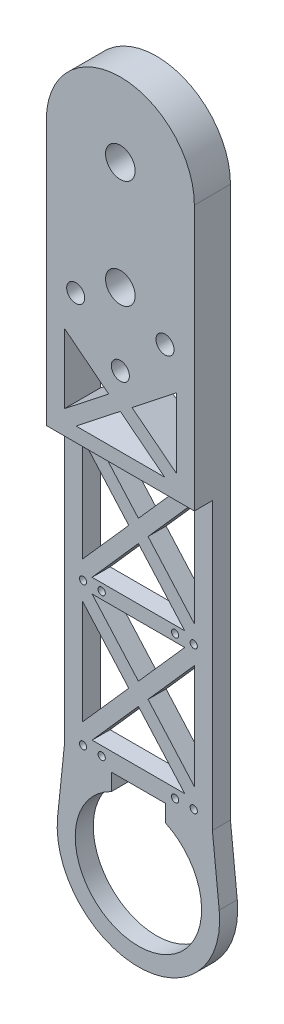
SolidWorks part; units mm, degrees
ref_plane "정면" through (0, 0, 0) normal (0, 0, 1) x (1, 0, 0)
ref_plane "윗면" through (0, 0, 0) normal (0, 1, 0) x (1, 0, 0)
ref_plane "우측면" through (0, 0, 0) normal (1, 0, 0) x (0, 0, -1)
sketch "스케치1" plane through (0, 0, 0) normal (0, 0, 1) x (1, 0, 0)
  line L0 (-20.5, 0) -> (-20.5, 173)
  line L1 (20.5, 0) -> (20.5, 173)
  line L2 (20.5, 173) -> (-20.5, 173) construction
  line L3 (-20.5, 143) -> (20.5, 143) construction
  circle A0 centre (0, 0) radius 20.5
  circle A1 centre (0, 0) radius 15.5 construction
  circle A2 centre (-15.5, 0) radius 1.5
  circle A3 centre (-7.75, 13.4234) radius 1.5
  circle A4 centre (7.75, 13.4234) radius 1.5
  circle A5 centre (15.5, 0) radius 1.5
  circle A6 centre (7.75, -13.4234) radius 1.5
  circle A7 centre (-7.75, -13.4234) radius 1.5
  circle A8 centre (0, -7) radius 6.5
  circle A9 centre (0, 173) radius 20.5
  point P19 (0, 0)
  dimension "D1" = 31
  dimension "D2" = 3
  dimension "D4" = 13
  dimension "D6" = 5
  dimension "D5" = 7
  dimension "D7" = 180
  dimension "D8" = 30
  dimension "D3" = 6
extrude "보스-돌출1" add sketch "스케치1" against normal blind 10 contours A9 L0 A0 L1 | A9 | A0 A8 A7 A6 A5 A4 A3 A2 region at (0, 86.5, 0) region at (0, 0.8114, 0) region at (0, 173, 0)
sketch "스케치2" plane through (0, 0, 0) normal (0, 0, 1) x (1, 0, 0)
  line L0 (-20.5, 143) -> (20.5, 143) construction
  circle A0 centre (0, 173) radius 4.1
  circle A1 centre (0, 143) radius 4.1
  dimension "D1" = 8.2
  dimension "D2" = 8.2
extrude "컷-돌출1" cut sketch "스케치2" against normal blind 10
sketch "스케치3" plane through (0, 0, 0) normal (0, 0, 1) x (1, 0, 0)
  line L0 (-20.5, 133) -> (20.5, 133) construction
  line L1 (-20.5, 0) -> (-20.5, 173) construction
  line L2 (20.5, 0) -> (20.5, 173) construction
  line L3 (-15.5, 128) -> (15.5, 103.625) construction
  line L4 (-20.5, 143) -> (20.5, 143) construction
  line L5 (-20.5, 20.5) -> (20.5, 20.5) construction
  line L6 (-15.5, 128) -> (15.5, 128)
  line L7 (-15.5, 128) -> (-15.5, 25.5)
  line L8 (-15.5, 25.5) -> (15.5, 25.5)
  line L9 (15.5, 128) -> (15.5, 25.5)
  line L10 (-15.5, 125.4558) -> (12.2643, 103.625)
  line L11 (-12.2643, 128) -> (15.5, 106.1692)
  line L12 (15.5, 128) -> (-15.5, 103.625) construction
  line L13 (12.2643, 128) -> (-15.5, 106.1692)
  line L14 (15.5, 125.4558) -> (-12.2643, 103.625)
  line L15 (-15.5, 99.625) -> (15.5, 99.625)
  line L16 (-15.5, 62.56) -> (15.5, 62.56) construction
  line L17 (-15.5, 64.56) -> (15.5, 64.56)
  line L18 (-15.5, 60.56) -> (15.5, 60.56)
  line L19 (-15.5, 99.625) -> (15.5, 64.56) construction
  line L20 (-15.5, 64.56) -> (15.5, 99.625) construction
  line L21 (15.5, 60.56) -> (-15.5, 25.5) construction
  line L22 (-15.5, 60.56) -> (15.5, 25.5) construction
  line L23 (-12.8305, 99.625) -> (15.5, 67.5796)
  line L24 (15.5, 103.625) -> (-15.5, 103.625)
  line L25 (-15.5, 96.6054) -> (12.8305, 64.56)
  line L26 (12.8305, 99.625) -> (-15.5, 67.5796)
  line L27 (15.5, 96.6054) -> (-12.8305, 64.56)
  line L28 (-12.8303, 60.56) -> (15.5, 28.5193)
  line L29 (-15.5, 57.5407) -> (12.8303, 25.5)
  line L30 (12.8303, 60.56) -> (-15.5, 28.5193)
  line L31 (15.5, 57.5407) -> (-12.8303, 25.5)
  circle A0 centre (0, 0) radius 20.5 construction
  point P6 (0, 71.75)
  dimension "D1" = 10
  dimension "D2" = 5
  dimension "D3" = 5
  dimension "D4" = 5
  dimension "D5" = 5
  dimension "D6" = 20.5
  dimension "D7" = 24.375
  dimension "D8" = 2
  dimension "D9" = 2
  dimension "D10" = 2
  dimension "D11" = 2
  dimension "D12" = 4
  dimension "D13" = 37.065
  dimension "D14" = 2
  dimension "D15" = 2
  dimension "D16" = 2
  dimension "D17" = 2
  dimension "D18" = 2
  dimension "D19" = 2
  dimension "D20" = 2
  dimension "D21" = 2
  dimension "D22" = 2
  dimension "D23" = 2
sketch "스케치4" plane through (0, 0, 0) normal (0, 0, 1) x (1, 0, 0)
  line L7 (-20.5, 0) -> (-20.5, 173) construction
  line L8 (20.5, -20.5) -> (-20.5, -20.5)
  line L9 (20.5, -20.5) -> (20.5, 99.625)
  line L10 (20.5, 99.625) -> (-20.5, 99.625)
  line L11 (-20.5, -20.5) -> (-20.5, 99.625)
  line L12 (-15.5, 99.625) -> (15.5, 99.625) construction
  dimension "D1" = 0
extrude "컷-돌출3" cut sketch "스케치4" against normal blind 5
extrude "컷-돌출4" cut sketch "스케치3" against normal blind 10 and the other way through all contours L9 L14 L11 | L24 L10 L14 | L13 L10 L7 region at (-11.4119, 115.8125, 0) region at (11.4119, 115.8125, 0) region at (0, 106.8394, 0)
extrude "컷-돌출5" cut sketch "스케치3<4>" against normal blind 10 and the other way through all contours L26 L15 L23 | L9 L27 L23 | L25 L27 L17 | L26 L25 L7 | L30 L18 L28 | L30 L29 L7 | L29 L31 L8 | L9 L31 L28 region at (-11.2232, 82.0925, 0) region at (0, 94.7874, 0) region at (11.2232, 82.0925, 0) region at (0, 69.3976, 0) region at (-11.2232, 43.03, 0) region at (0, 55.7231, 0) region at (11.2232, 43.03, 0) region at (0, 30.3369, 0)
sketch "스케치3<4>" plane through (0, 0, 0) normal (0, 0, 1) x (1, 0, 0) same geometry as "스케치3"
sketch "스케치5" plane through (0, 0, 0) normal (0, 0, 1) x (1, 0, 0)
  line L1 (-20.5, 20.5) -> (20.5, 20.5)
  line L2 (-20.5, 20.5) -> (-20.5, -20.5)
  line L3 (-20.5, -20.5) -> (20.5, -20.5)
  line L4 (20.5, 20.5) -> (20.5, -20.5)
extrude "컷-돌출6" cut sketch "스케치5" against normal blind 10
sketch "스케치6" plane through (0, 0, 0) normal (0, 0, 1) x (1, 0, 0)
  line L0 (-20.5, 20.5) -> (20.5, 20.5)
  line L1 (-20.5, 20.5) -> (-22.3806, 2.3145)
  line L2 (20.5, 20.5) -> (22.3806, 2.3145)
  line L3 (-7.5, 20.5) -> (-7.5, 15.8114)
  line L4 (7.5, 20.5) -> (7.5, 15.8114)
  circle A1 centre (0, 0) radius 17.5
  circle A2 centre (0, 0) radius 22.5
  dimension "D1" = 35
  dimension "D3" = 20.5
  dimension "D4" = 7.5
  dimension "D5" = 7.5
  dimension "D2" = 5
extrude "보스-돌출2" add sketch "스케치6" against normal up to surface (10 mm away) from surface contours A2 L0 L1 | A2 L0 L4 A1 L3 | A2 L2 L0 region at (-8.1224, 18.1557, 0) region at (-17.8491, 16.2965, 0) region at (17.8491, 16.2965, 0) up to face at (0, 69.3976, -10) starting at face at (0, 74.9446, -5)
sketch "스케치7" plane through (0, 0, -5) normal (0, 0, 1) x (1, 0, 0)
  line L0 (-20.5, 99.625) -> (-20.5, 20.5) construction
  line L1 (20.5, 20.5) -> (20.5, 99.625) construction
  line L2 (-20.5, 20.5) -> (20.5, 20.5) construction
  line L3 (-15.5, 62.56) -> (15.5, 62.56) construction
  circle A0 centre (-15.33, 23) radius 1
  circle A1 centre (-10.16, 23) radius 1
  circle A2 centre (10.16, 23) radius 1
  circle A3 centre (15.33, 23) radius 1
  circle A4 centre (-15.33, 62.56) radius 1
  circle A5 centre (-10.16, 62.56) radius 1
  circle A6 centre (10.16, 62.56) radius 1
  circle A7 centre (15.33, 62.56) radius 1
  dimension "D1" = 2
  dimension "D2" = 2
  dimension "D3" = 2
  dimension "D4" = 2
  dimension "D13" = 2
  dimension "D14" = 2
  dimension "D15" = 2
  dimension "D16" = 2
  dimension "D5" = 5.17
  dimension "D6" = 5.17
  dimension "D7" = 5.17
  dimension "D8" = 5.17
  dimension "D9" = 2.5
  dimension "D10" = 2.5
  dimension "D11" = 2.5
  dimension "D12" = 2.5
  dimension "D17" = 5.17
  dimension "D18" = 5.17
  dimension "D19" = 5.17
  dimension "D20" = 5.17
extrude "컷-돌출7" cut sketch "스케치7" against normal through all
sketch "스케치8" plane through (0, 0, 0) normal (0, 0, 1) x (1, 0, 0)
  line L0 (-20.5, 0) -> (-20.5, 173) construction
  line L1 (-20.5, 143) -> (20.5, 143) construction
  line L3 (20.5, 99.625) -> (20.5, 173) construction
  circle A0 centre (-12.37, 135.5) radius 2.5
  circle A1 centre (0, 123) radius 2.5
  circle A3 centre (0, 143) radius 4.1 construction
  circle A4 centre (12.37, 135.5) radius 2.5
  dimension "D1" = 5
  dimension "D4" = 5
  dimension "D5" = 20
  dimension "D6" = 5
  dimension "D2" = 8.13
  dimension "D3" = 7.5
  dimension "D7" = 8.13
  dimension "D8" = 7.5
extrude "컷-돌출8" cut sketch "스케치8" against normal blind 10
sketch "스케치9" plane through (0, 0, 0) normal (0, 0, 1) x (1, 0, 0)
  circle A0 centre (0, 173) radius 5
  circle A1 centre (0, 143) radius 5
  dimension "D1" = 10
  dimension "D2" = 10
extrude "컷-돌출9" cut sketch "스케치9" along normal blind 1.8 from surface starting at face at (-9.87, 135.5, -10)
fillet "필렛1" radius 0.2 4 edges at (4.1, 143, -8.2) (5, 143, -10) (4.1, 173, -8.2) (5, 173, -10)
